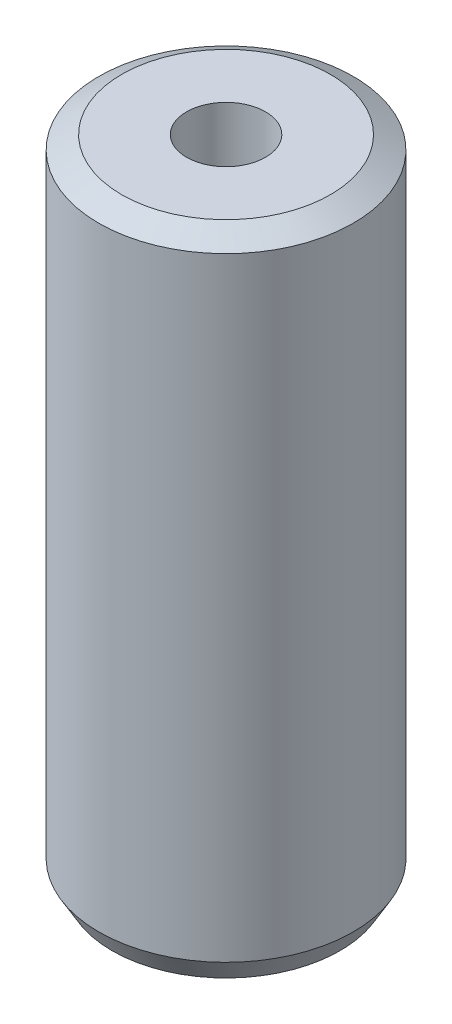
SolidWorks part; units mm, degrees
ref_plane "Front Plane" through (0, 0, 0) normal (0, 0, 1) x (1, 0, 0)
ref_plane "Top Plane" through (0, 0, 0) normal (0, 1, 0) x (1, 0, 0)
ref_plane "Right Plane" through (0, 0, 0) normal (1, 0, 0) x (0, 0, -1)
sketch "Sketch1" plane through (0, 0, 0) normal (0, 1, 0) x (1, 0, 0)
  circle A0 centre (0, 0) radius 17.5
  dimension "SHAFT_OD" = 35
extrude "Boss-Extrude1" add sketch "Sketch1" along normal blind 89.3925
sketch "Sketch2" plane through (0, 0, 0) normal (0, 1, 0) x (1, 0, 0)
  circle A0 centre (0, 0) radius 5.4274
  dimension "BORE_D" = 10.8548
extrude "Cut-Extrude1" cut sketch "Sketch2" along normal through all
chamfer "Chamfer1" distance 1.8203 angle 60 2 edges at (0, 89.3925, 17.5) (0, 0, 17.5) first distance on face at (0, 89.3925, 17.5) first distance on face at (0, 0, 5.4274)
